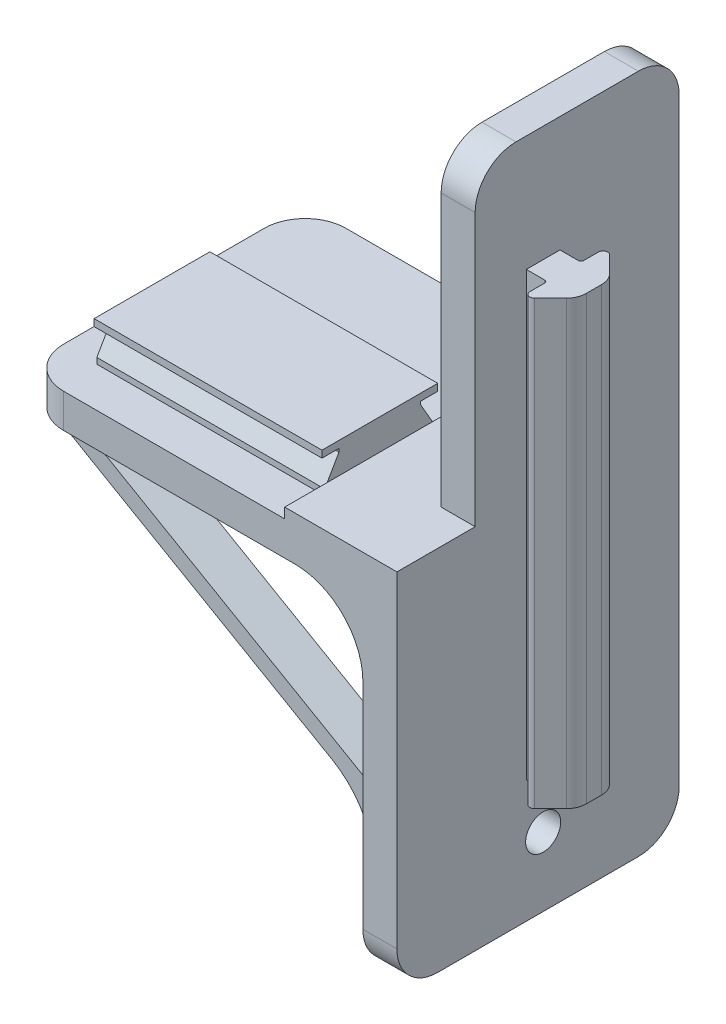
SolidWorks part; units mm, degrees
ref_plane "Front Plane" through (0, 0, 0) normal (0, 0, 1) x (1, 0, 0)
ref_plane "Top Plane" through (0, 0, 0) normal (0, 1, 0) x (1, 0, 0)
ref_plane "Right Plane" through (0, 0, 0) normal (1, 0, 0) x (0, 0, -1)
ref_plane "Plane3" through (0, 275, 0) normal (0, 1, 0) x (1, 0, 0)
sketch "Sketch1" plane through (0, 275, 0) normal (0, 1, 0) x (1, 0, 0)
  line L0 (389.6298, -111.5897) -> (387.1298, -111.5897)
  line L1 (389.6298, -106.6597) -> (387.1298, -106.6597)
  line L2 (387.1298, -106.6597) -> (387.1298, -111.5897)
  line L7 (390.3298, -111.6997) -> (389.6298, -111.6997) construction
  line L8 (389.6298, -106.5497) -> (390.3298, -106.5497) construction
  line L9 (390.6298, -114.1689) -> (390.6298, -111.9997) construction
  line L10 (394.3011, -112.3806) -> (391.9613, -114.7204) construction
  line L11 (395.1798, -107.9902) -> (395.1798, -110.2593) construction
  line L12 (390.6298, -106.2497) -> (390.6298, -104.0806) construction
  line L13 (391.9613, -103.5291) -> (394.3011, -105.8689) construction
  line L14 (389.6298, -106.6597) -> (390.3298, -106.6597)
  line L15 (390.7398, -106.2497) -> (390.7398, -104.0806)
  line L16 (391.8836, -103.6069) -> (394.2233, -105.9466)
  line L17 (395.0698, -107.9902) -> (395.0698, -110.2593)
  line L18 (394.2233, -112.3028) -> (391.8836, -114.6426)
  line L19 (390.7398, -114.1689) -> (390.7398, -111.9997)
  line L20 (390.3298, -111.5897) -> (389.6298, -111.5897)
  arc A6 (390.6298, -111.9997) -> (390.3298, -111.6997) centre (390.3298, -111.9997) ccw construction
  arc A7 (390.3298, -106.5497) -> (390.6298, -106.2497) centre (390.3298, -106.2497) ccw construction
  arc A8 (390.6298, -114.1689) -> (391.9613, -114.7204) centre (391.4098, -114.1689) ccw construction
  arc A9 (394.3011, -112.3806) -> (395.1798, -110.2593) centre (392.1798, -110.2593) ccw construction
  arc A10 (395.1798, -107.9902) -> (394.3011, -105.8689) centre (392.1798, -107.9902) ccw construction
  arc A11 (391.9613, -103.5291) -> (390.6298, -104.0806) centre (391.4098, -104.0806) ccw construction
  arc A12 (390.3298, -106.6597) -> (390.7398, -106.2497) centre (390.3298, -106.2497) ccw
  arc A13 (391.8836, -103.6069) -> (390.7398, -104.0806) centre (391.4098, -104.0806) ccw
  arc A14 (395.0698, -107.9902) -> (394.2233, -105.9466) centre (392.1798, -107.9902) ccw
  arc A15 (394.2233, -112.3028) -> (395.0698, -110.2593) centre (392.1798, -110.2593) ccw
  arc A16 (390.7398, -114.1689) -> (391.8836, -114.6426) centre (391.4098, -114.1689) ccw
  arc A17 (390.7398, -111.9997) -> (390.3298, -111.5897) centre (390.3298, -111.9997) ccw
  dimension "D2" = 2.5
  dimension "D1" = 0.11
ref_plane "Plane6" through (0, 245, 0) normal (0, 1, 0) x (1, 0, 0)
sketch "Sketch9" plane through (0, 245, 0) normal (0, 1, 0) x (1, 0, 0)
  line L0 (389.6298, -111.5997) -> (387.6298, -111.5997)
  line L1 (387.6298, -106.6497) -> (387.6298, -111.5997)
  line L7 (390.3298, -111.6897) -> (389.6298, -111.6897) construction
  line L8 (390.6298, -114.1589) -> (390.6298, -111.9897) construction
  line L9 (394.3011, -112.3706) -> (391.9613, -114.7104) construction
  line L10 (395.1798, -108.0002) -> (395.1798, -110.2493) construction
  line L11 (391.9613, -103.5391) -> (394.3011, -105.8789) construction
  line L12 (389.6298, -106.5597) -> (390.3298, -106.5597) construction
  line L13 (390.6298, -106.2597) -> (390.6298, -104.0906) construction
  line L14 (389.6298, -106.6497) -> (390.3298, -106.6497)
  line L15 (390.7198, -106.2597) -> (390.7198, -104.0906)
  line L16 (391.8977, -103.6027) -> (394.2375, -105.9425)
  line L17 (395.0898, -108.0002) -> (395.0898, -110.2493)
  line L18 (394.2375, -112.307) -> (391.8977, -114.6468)
  line L19 (390.7198, -114.1589) -> (390.7198, -111.9897)
  line L20 (390.3298, -111.5997) -> (389.6298, -111.5997)
  line L21 (389.6298, -106.6497) -> (387.6298, -106.6497)
  arc A6 (390.6298, -111.9897) -> (390.3298, -111.6897) centre (390.3298, -111.9897) ccw construction
  arc A7 (390.6298, -114.1589) -> (391.9613, -114.7104) centre (391.4098, -114.1589) ccw construction
  arc A8 (394.3011, -112.3706) -> (395.1798, -110.2493) centre (392.1798, -110.2493) ccw construction
  arc A9 (395.1798, -108.0002) -> (394.3011, -105.8789) centre (392.1798, -108.0002) ccw construction
  arc A10 (391.9613, -103.5391) -> (390.6298, -104.0906) centre (391.4098, -104.0906) ccw construction
  arc A11 (390.3298, -106.5597) -> (390.6298, -106.2597) centre (390.3298, -106.2597) ccw construction
  arc A12 (390.3298, -106.6497) -> (390.7198, -106.2597) centre (390.3298, -106.2597) ccw
  arc A13 (391.8977, -103.6027) -> (390.7198, -104.0906) centre (391.4098, -104.0906) ccw
  arc A14 (395.0898, -108.0002) -> (394.2375, -105.9425) centre (392.1798, -108.0002) ccw
  arc A15 (394.2375, -112.307) -> (395.0898, -110.2493) centre (392.1798, -110.2493) ccw
  arc A16 (390.7198, -114.1589) -> (391.8977, -114.6468) centre (391.4098, -114.1589) ccw
  arc A17 (390.7198, -111.9897) -> (390.3298, -111.5997) centre (390.3298, -111.9897) ccw
  dimension "D2" = 2
  dimension "D3" = 2
  dimension "D1" = 0.09
extrude "Boss-Extrude5" add sketch "Sketch9" against normal blind 50
ref_plane "Plane8" through (387.6298, 0, 0) normal (-1, 0, 0) x (0, 0, 1)
sketch "Sketch11" plane through (387.6298, 0, 0) normal (-1, 0, 0) x (0, 0, 1)
  line L1 (89.1247, 270) -> (130.6247, 270)
  line L2 (89.1247, 270) -> (89.1247, 170)
  line L3 (89.1247, 170) -> (130.6247, 170)
  line L4 (130.6247, 270) -> (130.6247, 170)
  line L5 (109.1247, 245) -> (109.1247, 188.6769) construction
  line L6 (106.6497, 245) -> (111.5997, 245) construction
  line L7 (106.6497, 220) -> (141.9101, 220) construction
  line L8 (106.6497, 195) -> (106.6497, 245) construction
  dimension "D1" = 20
  dimension "D2" = 21.5
  dimension "D3" = 50
  dimension "D4" = 50
extrude "Boss-Extrude6" add sketch "Sketch11" along normal blind 5
sketch "Sketch12" plane through (387.6298, 0, 0) normal (-1, 0, 0) x (0, 0, 1)
  line L0 (130.6247, 220) -> (89.1247, 220) construction
  line L1 (130.6247, 170) -> (130.6247, 270) construction
  line L2 (89.1247, 270) -> (89.1247, 170) construction
  line L3 (130.6247, 170) -> (130.6247, 270) construction
  line L4 (130.6247, 222.5) -> (89.1247, 222.5)
  line L5 (130.6247, 222.5) -> (130.6247, 217.5)
  line L6 (130.6247, 217.5) -> (89.1247, 217.5)
  line L7 (89.1247, 222.5) -> (89.1247, 217.5)
  dimension "D1" = 2.5
  dimension "D2" = 2.5
extrude "Boss-Extrude8" add sketch "Sketch12" along normal blind 55
sketch "Sketch13" plane through (387.6298, 0, 0) normal (-1, 0, 0) x (0, 0, 1)
  line L0 (119.1247, 5) -> (119.1247, 405) construction
  line L1 (119.1247, 222.5) -> (119.1247, 270)
  line L2 (89.1247, 222.5) -> (130.6247, 222.5) construction
  line L3 (119.1247, 222.5) -> (130.6247, 222.5)
  line L4 (130.6247, 222.5) -> (130.6247, 270) construction
  line L5 (130.6247, 270) -> (89.1247, 270) construction
  line L6 (130.6247, 222.5) -> (130.6247, 270)
  line L7 (130.6247, 270) -> (119.1247, 270)
extrude "Cut-Extrude1" cut sketch "Sketch13" along normal blind 55
ref_plane "Plane9" through (0, 0, 129.1247) normal (0, 0, 1) x (1, 0, 0)
sketch "Sketch15" plane through (0, 0, 129.1247) normal (0, 0, 1) x (1, 0, 0)
  line L0 (335.6298, 217.5) -> (382.6298, 190.3645)
  line L1 (332.6298, 217.5) -> (382.6298, 217.5) construction
  line L2 (382.6298, 170) -> (382.6298, 217.5) construction
  line L3 (332.6298, 217.5) -> (382.6298, 217.5) construction
  line L4 (335.6298, 217.5) -> (340.6298, 217.5)
  line L7 (382.6298, 190.3645) -> (382.6298, 193.2513)
  line L8 (340.6298, 217.5) -> (382.6298, 193.2513)
  point P6 (332.6298, 217.5)
  dimension "D1" = 3
  dimension "D2" = 30
  dimension "D3" = 5
  dimension "D4" = 30
ref_plane "Plane10" through (332.6298, 0, 0) normal (-1, 0, 0) x (0, 0, 1)
ref_plane "Plane11" through (382.6298, 0, 0) normal (-1, 0, 0) x (0, 0, 1)
extrude "Boss-Extrude9" add sketch "Sketch15" against normal blind 6
fillet "Fillet7" radius 12 2 edges at (335.6298, 217.5, 126.1247) (382.6298, 190.3645, 126.1247)
ref_plane "Plane12" through (0, 0, 110.6247) normal (0, 0, 1) x (1, 0, 0)
mirror "Mirror1" about plane through (0, 0, 110.6247) normal (0, 0, 1) of "Boss-Extrude9", "Fillet7"
fillet "Fillet8" radius 6 6 edges at (385.1298, 170, 89.1247) (385.1298, 170, 130.6247) (332.6298, 220, 89.1247) (332.6298, 220, 130.6247) (385.1298, 270, 89.1247) (385.1298, 270, 119.1247)
extrude "Boss-Extrude10" add sketch "Sketch9<2>" along normal blind 8
sketch "Sketch9<2>" plane through (0, 245, 0) normal (0, 1, 0) x (1, 0, 0) same geometry as "Sketch9"
fillet "Fillet12" radius 10 1 edges at (382.6298, 217.5, 109.8747)
extrude "Boss-Extrude11" add sketch "Sketch9<3>" against normal blind 57
sketch "Sketch9<3>" plane through (0, 245, 0) normal (0, 1, 0) x (1, 0, 0) same geometry as "Sketch9"
ref_plane "Plane13" through (382.6298, 0, 0) normal (-1, 0, 0) x (0, 0, 1)
sketch "Sketch16" plane through (382.6298, 0, 0) normal (-1, 0, 0) x (0, 0, 1)
  line L1 (111.6997, 5) -> (111.6997, 405) construction
  line L3 (111.6997, 5) -> (111.6997, 405) construction
  line L4 (111.6997, 5) -> (111.6997, 405) construction
  line L5 (111.6997, 5) -> (111.6997, 405) construction
  line L6 (106.5497, 5) -> (106.5497, 405) construction
  line L7 (106.5497, 5) -> (106.5497, 405) construction
  line L9 (109.1247, 162.2841) -> (109.1247, 197.982) construction
  circle A0 centre (109.1247, 180.1331) radius 2.575
  dimension "D2" = 5.15
extrude "Cut-Extrude2" cut sketch "Sketch16" against normal blind 10
sketch "Sketch17" plane through (371.1298, 0, 0) normal (1, 0, 0) x (0, 0, -1)
  line L2 (-103.1446, 222.5) -> (-103.1446, 224)
  line L3 (-130.6247, 222.5) -> (-103.1446, 222.5)
  line L4 (-130.6247, 224) -> (-130.6247, 222.5)
  line L5 (-130.6247, 224) -> (-103.1446, 224)
  dimension "D1" = 1.5
extrude "Boss-Extrude12" add sketch "Sketch17" along normal up to surface (11.5 mm away) up to face at (382.6298, 252.5809, 104.1247)
sketch "Sketch18" plane through (382.6298, 0, 0) normal (1, 0, 0) x (0, 0, -1)
  line L0 (-119.1247, 222.5) -> (-119.1247, 224) construction
  line L1 (-130.6247, 224) -> (-119.1247, 224) construction
  line L2 (-119.1247, 222.5) -> (-130.6247, 222.5) construction
  line L3 (-130.6247, 222.5) -> (-130.6247, 224) construction
  line L4 (-119.1247, 222.5) -> (-119.1247, 224)
  line L5 (-130.6247, 224) -> (-119.1247, 224)
  line L6 (-119.1247, 222.5) -> (-130.6247, 222.5)
  line L7 (-130.6247, 222.5) -> (-130.6247, 224)
extrude "Boss-Extrude13" add sketch "Sketch18" along normal up to surface (5 mm away) up to face at (387.6298, 177.5581, 109.1247)
sketch "Sketch19" plane through (332.6298, 0, 0) normal (-1, 0, 0) x (0, 0, 1)
  line L12 (125.1447, 227.49) -> (125.1447, 228.51)
  line L13 (122.6447, 227.49) -> (125.1447, 227.49)
  line L14 (122.6447, 227.0027) -> (122.6447, 227.49)
  line L15 (124.745, 223.3679) -> (122.6447, 227.0027)
  line L16 (124.745, 222.5) -> (124.745, 223.3679)
  line L17 (108.5243, 222.5) -> (124.745, 222.5)
  line L18 (108.5243, 223.3679) -> (108.5243, 222.5)
  line L19 (110.6247, 227.0027) -> (108.5243, 223.3679)
  line L20 (110.6247, 227.49) -> (110.6247, 227.0027)
  line L21 (108.1247, 227.49) -> (110.6247, 227.49)
  line L22 (108.1247, 228.51) -> (108.1247, 227.49)
  line L23 (125.1447, 228.51) -> (108.1247, 228.51)
extrude "Boss-Extrude14" add sketch "Sketch19" against normal up to surface (33.5 mm away) from offset 5 offset against normal yes
